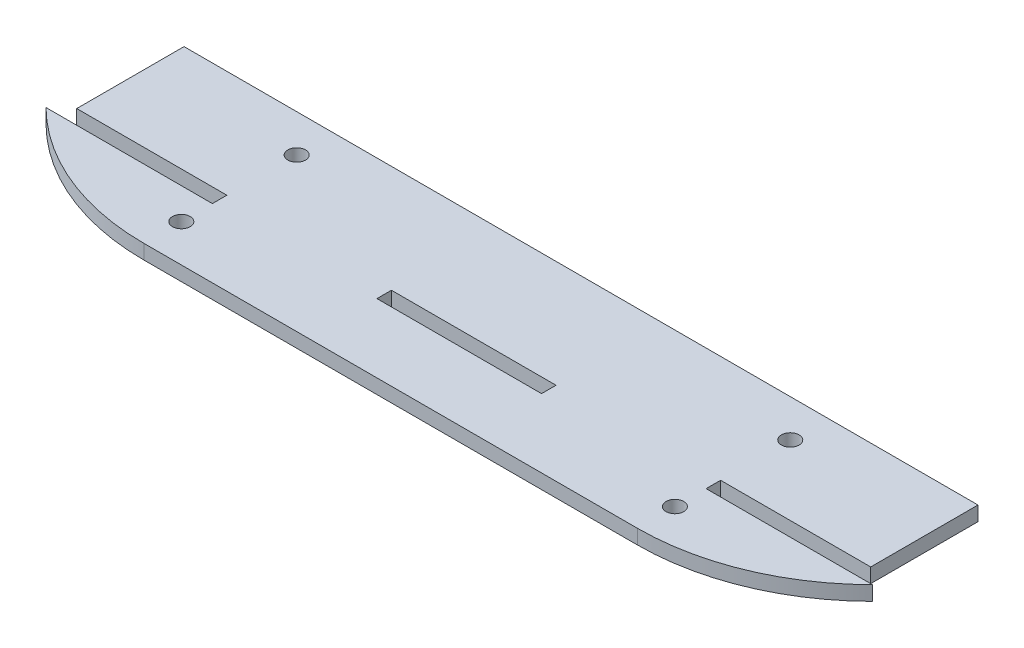
SolidWorks part; units mm, degrees
ref_plane "Ön Düzlem" through (0, 0, 0) normal (0, 0, 1) x (1, 0, 0)
ref_plane "Üst Düzlem" through (0, 0, 0) normal (0, 1, 0) x (1, 0, 0)
ref_plane "Sağ Düzlem" through (0, 0, 0) normal (1, 0, 0) x (0, 0, -1)
sketch "Sketch1" plane through (0, 0, 0) normal (0, 1, 0) x (1, 0, 0)
  line L1 (-46, 0) -> (46, 0)
  line L17 (-73.9952, 35.5) -> (73.9952, 35.5)
  line L19 (-73.9952, 35.5) -> (-73.9952, 15.5)
  line L21 (73.9952, 35.5) -> (73.9952, 15.5)
  line L22 (-15.34, 15.5) -> (-15.34, 12.8)
  line L23 (-46.0152, 15.5) -> (-46.0152, 12.8)
  line L24 (-15.34, 12.8) -> (15.34, 12.8)
  line L25 (15.34, 12.8) -> (15.34, 15.5)
  line L26 (15.34, 15.5) -> (-15.34, 15.5)
  line L29 (46.0152, 15.5) -> (46.0152, 12.8)
  line L31 (46.0152, 15.5) -> (73.9952, 15.5)
  line L32 (77.0252, 12.8) -> (46.0152, 12.8)
  line L33 (-46.0152, 15.5) -> (-73.9952, 15.5)
  line L34 (-46.0152, 12.8) -> (-77.0252, 12.8)
  arc A0 (-77.0252, 12.8) -> (-46, 0) centre (-46, 44) ccw
  arc A1 (46, 0) -> (77.0252, 12.8) centre (46, 44) ccw
  circle A2 centre (46, 28.5) radius 1.65
  circle A3 centre (46, 7) radius 1.65
  circle A4 centre (-46, 7) radius 1.65
  circle A5 centre (-46, 28.5) radius 1.65
extrude "Boss-Extrude1" add sketch "Sketch1" along normal blind 2.7
